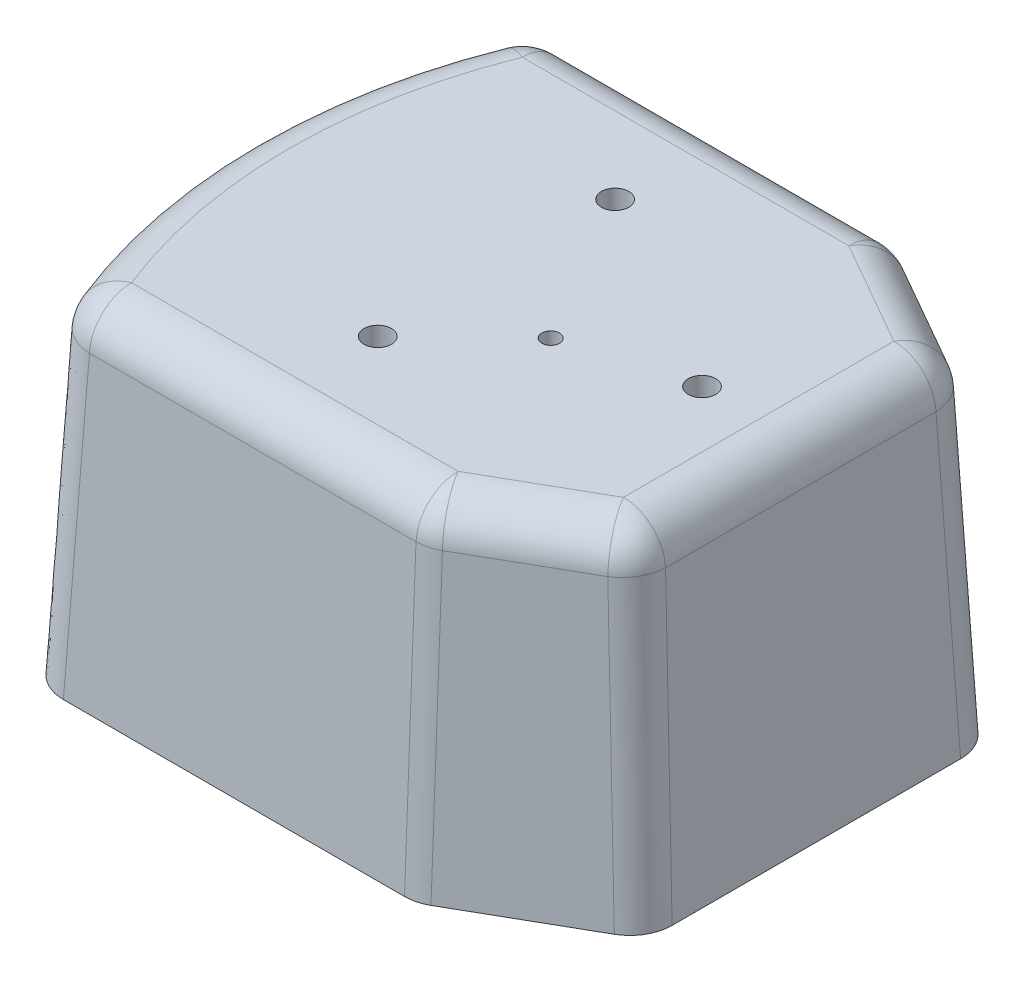
SolidWorks part; units mm, degrees
ref_plane "Front" through (0, 0, 0) normal (0, 0, 1) x (1, 0, 0)
ref_plane "Top" through (0, 0, 0) normal (0, 1, 0) x (1, 0, 0)
ref_plane "Right" through (0, 0, 0) normal (1, 0, 0) x (0, 0, -1)
sketch "Sketch1" plane through (0, 0, 0) normal (0, 1, 0) x (1, 0, 0)
  line L0 (-58.6146, 67.5) -> (-58.6146, -67.5) construction
  line L2 (-62.5, -60) -> (-62.5, 60)
  line L5 (-62.5, -60) -> (62.5, 60) construction
  line L6 (-62.5, 60) -> (62.5, -60) construction
  line L7 (62.5, 0) -> (-58.6146, 0) construction
  line L8 (-62.5, 60) -> (27.5, 60)
  line L9 (27.5, 60) -> (62.5, 40)
  line L10 (62.5, 40) -> (62.5, -40)
  line L12 (27.5, -60) -> (-62.5, -60)
  line L13 (27.5, 60) -> (62.5, 60) construction
  line L14 (62.5, 60) -> (62.5, 40) construction
  line L15 (27.5, -60) -> (62.5, -60) construction
  line L16 (62.5, -60) -> (62.5, -40) construction
  line L17 (27.5, -60) -> (62.5, -40)
  arc A0 (-58.6146, 67.5) -> (-58.6146, -67.5) centre (62.5, 0) ccw
  point P0 (0, 0)
  dimension "D3" = 135
  dimension "D1" = 125
  dimension "D2" = 120
  dimension "D4" = 35
  dimension "D5" = 20
  dimension "D6" = 20
extrude "Boss-Extrude1" add sketch "Sketch1" along normal blind 80 draft 3 contours L2 A0 | L2 region at (-67.9854, 0, 0) region at (-2.4883, 0, 0)
sketch "Sketch3" plane through (0, 0, 0) normal (0, -1, 0) x (1, 0, 0)
  line L0 (-62.5, 60) -> (27.5, 60) construction
  line L1 (27.5, 60) -> (62.5, 40) construction
  line L2 (62.5, 40) -> (62.5, -40) construction
  line L3 (62.5, -40) -> (27.5, -60) construction
  line L4 (27.5, -60) -> (-62.5, -60) construction
  line L5 (-62.5, -60) -> (-62.5, 60) construction
  line L6 (-57.4728, 58.5) -> (27.1017, 58.5)
  line L7 (27.1017, 58.5) -> (57.5, 41.1295)
  line L8 (57.5, 41.1295) -> (57.5, -41.1295)
  line L9 (57.5, -41.1295) -> (27.1017, -58.5)
  line L10 (27.1017, -58.5) -> (-57.4728, -58.5)
  line L11 (-57.4728, -58.5) -> (-57.4728, 58.5) construction
  arc A0 (-62.5, 60) -> (-62.5, -60) centre (62.5, 0) ccw construction
  arc A1 (-57.4728, 58.5) -> (-57.4728, -58.5) centre (57.5, 0) ccw
  dimension "D6" = 129
  dimension "D1" = 3
  dimension "D2" = 10
  dimension "D3" = 3
  dimension "D4" = 3
  dimension "D5" = 3
extrude "Cut-Extrude1" cut sketch "Sketch3" against normal blind 75 draft 3
fillet "Fillet1" radius 10 12 edges at (42.347, 80, 46.6872) (58.3074, 80, 0) (42.347, 80, -46.6872) (-16.7234, 80, -55.8074) (-71.9616, 80, 0) (-16.7234, 80, 55.8074) (60.4037, 40, 38.7835) (26.9433, 40, 57.9037) (60.4037, 40, -38.7835) (26.9433, 40, -57.9037)
sketch "Sketch4" plane through (0, 0, 0) normal (0, -1, 0) x (1, 0, 0)
  line L0 (-76.1542, 0) -> (62.5, 0) construction
  line L1 (62.5, -34.2047) -> (62.5, 34.2047) construction
  line L2 (-76.1542, 0) -> (-65.2509, -53.8954) construction
  line L3 (58.5, -25) -> (61.5, -25)
  line L4 (58.5, -25) -> (58.5, -34)
  line L5 (58.5, -34) -> (61.5, -34)
  line L6 (61.5, -25) -> (61.5, -34)
  line L7 (-68.4903, -29.0573) -> (-66.7057, -37.8786)
  line L8 (-66.7057, -37.8786) -> (-70.1362, -38.5726)
  line L9 (-70.1362, -38.5726) -> (-71.9208, -29.7513)
  line L10 (-71.9208, -29.7513) -> (-68.4903, -29.0573)
  line L11 (-68.4903, 29.0573) -> (-66.7057, 37.8786)
  line L12 (-66.7057, 37.8786) -> (-70.1362, 38.5726)
  line L13 (-70.1362, 38.5726) -> (-71.9208, 29.7513)
  line L14 (-71.9208, 29.7513) -> (-68.4903, 29.0573)
  line L15 (58.5, 34) -> (61.5, 34)
  line L16 (58.5, 25) -> (58.5, 34)
  line L17 (58.5, 25) -> (61.5, 25)
  line L18 (61.5, 25) -> (61.5, 34)
  arc A0 (-65.2509, 53.8954) -> (-65.2509, -53.8954) centre (62.5, 0) ccw construction
  point P16 (-70.2056, -29.4043)
  dimension "D1" = 1
  dimension "D2" = 25
  dimension "D3" = 9
  dimension "D4" = 3
  dimension "D5" = 9
  dimension "D6" = 3.5
  dimension "D7" = 30
extrude "Cut-Extrude2" cut sketch "Sketch4" against normal blind 5 draft 5
sketch "Sketch7" plane through (0, 0, 0) normal (0, -1, 0) x (1, 0, 0)
  line L0 (-56.0499, 60) -> (-56.0499, -60) construction
  line L1 (24.848, 60) -> (-56.0499, 60) construction
  line L2 (-76.1542, 0) -> (62.5, 0) construction
  line L3 (62.5, -34.2047) -> (62.5, 34.2047) construction
  line L4 (-58.0499, 51.1529) -> (-61.5669, 58.3384) construction
  line L5 (-58.0499, 51.1529) -> (-56.0499, 51.1529) construction
  arc A0 (-65.2509, 53.8954) -> (-65.2509, -53.8954) centre (62.5, 0) ccw construction
  circle A1 centre (-58.0499, 51.1529) radius 5
  circle A3 centre (-58.0499, -51.1529) radius 5
  spline S4 degree 3 poles (-56.0499, 60) (-57.0332, 60) (-57.9924, 59.858) (-59.1617, 59.5063) (-59.395, 59.4266) (-59.8521, 59.2515) (-60.0763, 59.156) (-60.7358, 58.8463) (-61.1584, 58.6088) (-61.9692, 58.072) (-62.3602, 57.7696) (-63.0859, 57.1177) (-63.422, 56.768) (-64.0417, 56.0218) (-64.3259, 55.6242) (-64.8365, 54.7848) (-65.0598, 54.3484) (-65.2509, 53.8954) knots 0 0 0 0 0.25 0.25 0.3125 0.3125 0.375 0.375 0.5 0.5 0.625 0.625 0.75 0.75 0.875 0.875 1 1 1 1 construction
  dimension "D2" = 10
  dimension "D1" = 2
  dimension "D3" = 8
  dimension "D4" = 8.8471
extrude "Cut-Extrude3" cut sketch "Sketch7" against normal blind 7
sketch "Mounting_Holes" plane through (0, 80, 0) normal (0, 1, 0) x (1, 0, 0)
  line L0 (-62.5, 60) -> (-62.5, -60) construction
  line L1 (-62.5, -60) -> (27.5, -60) construction
  line L2 (27.5, -60) -> (62.5, -40) construction
  line L3 (62.5, -40) -> (62.5, 40) construction
  line L4 (62.5, 40) -> (27.5, 60) construction
  line L5 (27.5, 60) -> (-62.5, 60) construction
  line L6 (62.5, 0) -> (2.5, 0) construction
  line L7 (2.5, 0) -> (2.5, -8) construction
  line L8 (2.5, -8) -> (7.5, -8) construction
  line L9 (2.8812, 0) -> (35.3812, 0) construction
  line L10 (2.8812, 0) -> (2.8812, -32.5) construction
  line L11 (2.8812, 0) -> (-13.3688, 28.1458) construction
  line L12 (48.8177, -32.0599) -> (48.8177, 32.0599) construction
  line L13 (48.8177, 11.5104) -> (-51.3435, -46.3177) construction
  line L14 (-13.3688, 28.1458) -> (7.5, -8) construction
  line L15 (23.8665, 46.3177) -> (-53.5718, 46.3177) construction
  line L16 (35.3812, 0) -> (-13.3688, -28.1458) construction
  line L17 (-38.3435, -46.3177) -> (48.8177, 4.0048) construction
  line L18 (-53.5718, -46.3177) -> (23.8665, -46.3177) construction
  line L20 (23.8665, -46.3177) -> (48.8177, -32.0599) construction
  line L23 (-27.6131, 46.3177) -> (25.373, -45.4569) construction
  line L25 (31.0166, -42.2319) -> (-20.1076, 46.3177) construction
  line L28 (-42.1542, -60) -> (-42.1542, -21.27) construction
  line L29 (-42.1542, -21.27) -> (-42.1542, -10.27) construction
  line L30 (-42.1542, -10.27) -> (-33.1542, -10.27) construction
  line L31 (-33.1542, -10.27) -> (-33.1542, -21.27) construction
  line L32 (-33.1542, -21.27) -> (-42.1542, -21.27) construction
  line L33 (-33.1542, -21.27) -> (-31.5942, -21.27) construction
  line L34 (-31.5942, -21.27) -> (-31.5942, -11.05) construction
  line L35 (-31.5942, -11.05) -> (-19.5542, -11.05) construction
  line L36 (-19.5542, -11.05) -> (-19.5542, -21.27) construction
  line L37 (-19.5542, -21.27) -> (-31.5942, -21.27) construction
  line L38 (24.848, -60) -> (-56.0499, -60) construction
  arc A0 (-62.5, -60) -> (-62.5, 60) centre (62.5, 0) cw construction
  circle A1 centre (7.5, -8) radius 2.1 construction
  circle A2 centre (2.8812, 0) radius 32.5 construction
  circle A3 centre (-13.3688, 28.1458) radius 3.25 construction
  circle A4 centre (35.3812, 0) radius 3.25 construction
  circle A6 centre (-13.3688, -28.1458) radius 3.25 construction
  point P33 (-51.3823, -46.3177)
  point P43 (-16.7262, 26.4741)
  point P45 (48.8177, 11.4836)
  point P46 (-19.5542, 46.3177)
  point P58 (-28.6726, 46.3177)
  point P61 (-76.1542, 0)
  dimension "D4" = 4.2
  dimension "D5" = 6.5
  dimension "D6" = 65
  dimension "D1" = 60
  dimension "D2" = 8
  dimension "D3" = 5
  dimension "D7" = 150
  dimension "D9" = 34
  dimension "D10" = 38.73
  dimension "D11" = 11
  dimension "D12" = 9
  dimension "D13" = 1.56
  dimension "D14" = 10.22
  dimension "D15" = 12.04
sketch "Sketch9" plane through (0, 80, 0) normal (0, 1, 0) x (1, 0, 0)
  circle A0 centre (-13.3688, 28.1458) radius 3.25
  circle A1 centre (35.3812, 0) radius 3.25
  circle A2 centre (-13.3688, -28.1458) radius 3.25
  circle A3 centre (7.5, -8) radius 2.1
  dimension "D1" = 4.2
  dimension "D2" = 6.5
extrude "CutExtrude_Mounting_Holes" cut sketch "Sketch9" against normal through all
